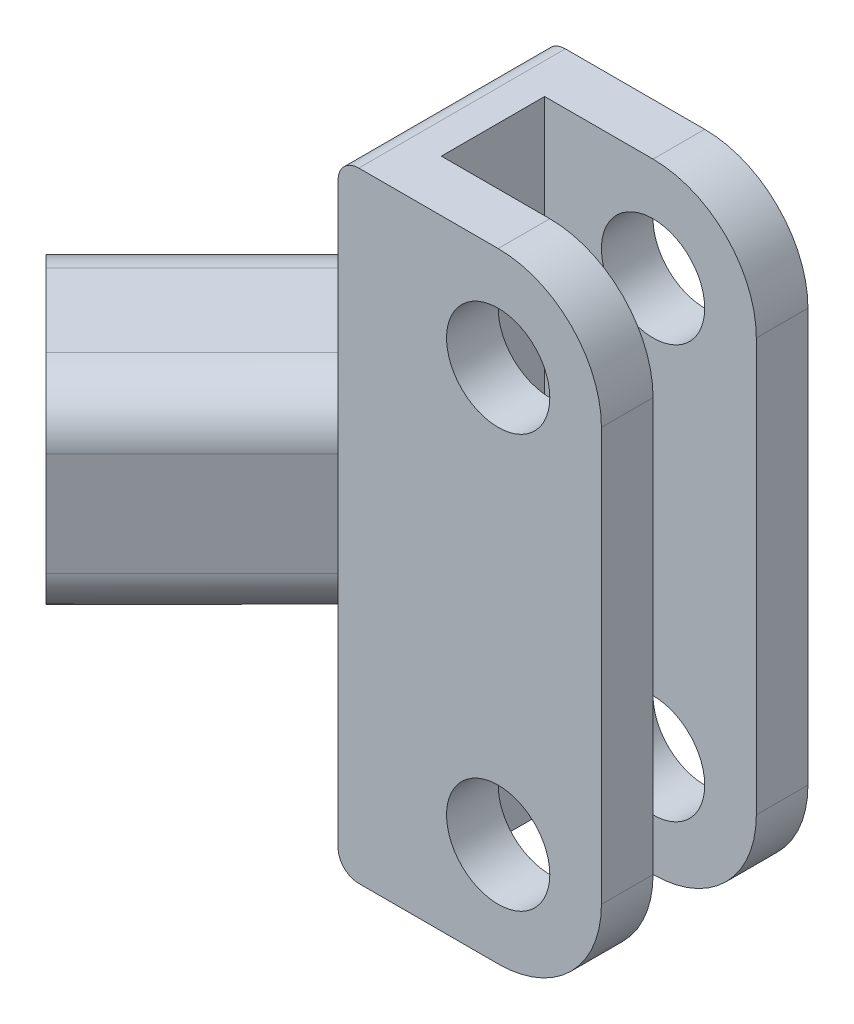
SolidWorks part; units mm, degrees
material "ABS"
ref_plane "Front Plane" through (0, 0, 0) normal (0, 0, 1) x (1, 0, 0)
ref_plane "Top Plane" through (0, 0, 0) normal (0, 1, 0) x (1, 0, 0)
ref_plane "Right Plane" through (0, 0, 0) normal (1, 0, 0) x (0, 0, -1)
ref_axis "X" through (-88.99, 0, 0) along (1, 0, 0)
ref_axis "Y" through (0, 55, 0) along (0, -1, 0)
ref_axis "Z" through (0, 0, -88.99) along (0, 0, 1)
sketch "Sketch1" plane through (0, 0, 0) normal (0, 0, 1) x (1, 0, 0)
  line L0 (0, 20) -> (0, -20) construction
  line L1 (-10.5, 30) -> (0, 30)
  line L2 (10, 20) -> (10, -20)
  line L3 (0, -30) -> (-10.5, -30)
  line L4 (-10.5, 30) -> (-10.5, -30)
  line L5 (-10.5, 30) -> (-15.5, 30)
  line L6 (-15.5, 30) -> (-15.5, -30)
  line L7 (-15.5, -30) -> (-10.5, -30)
  circle A0 centre (0, 20) radius 5
  circle A1 centre (0, -20) radius 5
  arc A2 (0, 30) -> (10, 20) centre (0, 20) cw
  arc A3 (10, -20) -> (0, -30) centre (0, -20) cw
  point P4 (0, 0)
  dimension "D1" = 40
  dimension "D2" = 10
  dimension "D3" = 5
  dimension "D4" = 10.5
  dimension "D5" = 5
extrude "Boss-Extrude1" add sketch "Sketch1" along normal mid plane 10 contours L6 L7 L4 L5 region at (-13, 0, 0)
extrude "Boss-Extrude2" add sketch "Sketch1<3>" along normal blind 5 from surface contours L6 L7 L4 L5 | A3 L2 A2 L1 L4 L3 A0 A1 region at (-0.6222, 0, 0) region at (-13, 0, 0) starting at face at (-13, 0, 5)
sketch "Sketch1<3>" plane through (0, 0, 0) normal (0, 0, 1) x (1, 0, 0) same geometry as "Sketch1"
extrude "Boss-Extrude3" add sketch "Sketch1<4>" against normal blind 5 from surface contours A3 L2 A2 L1 L4 L3 A0 A1 | L6 L7 L4 L5 region at (-0.6222, 0, 0) region at (-13, 0, 0) starting at face at (-13, 0, -5)
sketch "Sketch1<4>" plane through (0, 0, 0) normal (0, 0, 1) x (1, 0, 0) same geometry as "Sketch1"
sketch "Sketch3" plane through (0, 0, 0) normal (0, 1, 0) x (1, 0, 0)
  line L0 (-15.5, -10) -> (-15.5, 10) construction
  line L1 (-15.5, -10) -> (-15.5, 10)
  line L2 (-15.5, -10) -> (-29.6421, -24.1421)
  line L3 (-29.6421, -24.1421) -> (-43.7843, -10)
  line L5 (-29.6421, 4.1421) -> (-43.7843, -10)
  line L6 (-15.5, 10) -> (-12.0739, 10) construction
  arc A0 (-15.5, 10) -> (-29.6421, 4.1421) centre (-15.5, -10) ccw
  dimension "D1" = 20
  dimension "D2" = 20
  dimension "D3" = 45
extrude "Boss-Extrude4" add sketch "Sketch3" along normal mid plane 20
fillet "Fillet3" radius 5 6 edges at (-23.1537, -10, -8.4776) (-23.1537, 10, -8.4776) (-22.5711, -10, 17.0711) (-22.5711, 10, 17.0711) (-36.7132, -10, 2.9289) (-36.7132, 10, 2.9289)
fillet "Fillet2" radius 2 2 edges at (-15.5, -30, 0) (-15.5, 30, 0)
sketch "Sketch4" plane through (-26.8921, 0, 26.8921) normal (-0.7071, 0, 0.7071) x (0.7071, 0, 0.7071)
  line L4 (-23.8891, 0) -> (-3.8891, 0) construction
  line L8 (-18.8891, -10) -> (-8.8891, -10)
  line L9 (-3.8891, -5) -> (-3.8891, 5)
  line L10 (-8.8891, 10) -> (-18.8891, 10)
  line L11 (-23.8891, 5) -> (-23.8891, -5)
  line L12 (-18.8891, -10) -> (-8.8891, -10)
  line L13 (-3.8891, -5) -> (-3.8891, 5)
  line L14 (-8.8891, 10) -> (-18.8891, 10)
  line L15 (-23.8891, 5) -> (-23.8891, -5)
  circle A4 centre (-13.8891, 0) radius 7.5
  arc A8 (-8.8891, -10) -> (-3.8891, -5) centre (-8.8891, -5) ccw
  arc A9 (-3.8891, 5) -> (-8.8891, 10) centre (-8.8891, 5) ccw
  arc A10 (-18.8891, 10) -> (-23.8891, 5) centre (-18.8891, 5) ccw
  arc A11 (-23.8891, -5) -> (-18.8891, -10) centre (-18.8891, -5) ccw
  arc A12 (-8.8891, -10) -> (-3.8891, -5) centre (-8.8891, -5) ccw
  arc A13 (-3.8891, 5) -> (-8.8891, 10) centre (-8.8891, 5) ccw
  arc A14 (-18.8891, 10) -> (-23.8891, 5) centre (-18.8891, 5) ccw
  arc A15 (-23.8891, -5) -> (-18.8891, -10) centre (-18.8891, -5) ccw
  dimension "D2" = 15
  dimension "D1" = 0
extrude "Cut-Extrude1" cut sketch "Sketch4" against normal blind 15 contours A4 L4 | L4 A4 region at (-36.7132, -3.1831, 17.0711) region at (-36.7132, 3.1831, 17.0711)
mirror "Mirror1" [suppressed] about plane through (0, 0, 0) normal (0, 0, 1) of bodies 105
delete or keep bodies "Body-Delete/Keep 1" [suppressed] type delete bodies bodies 105
